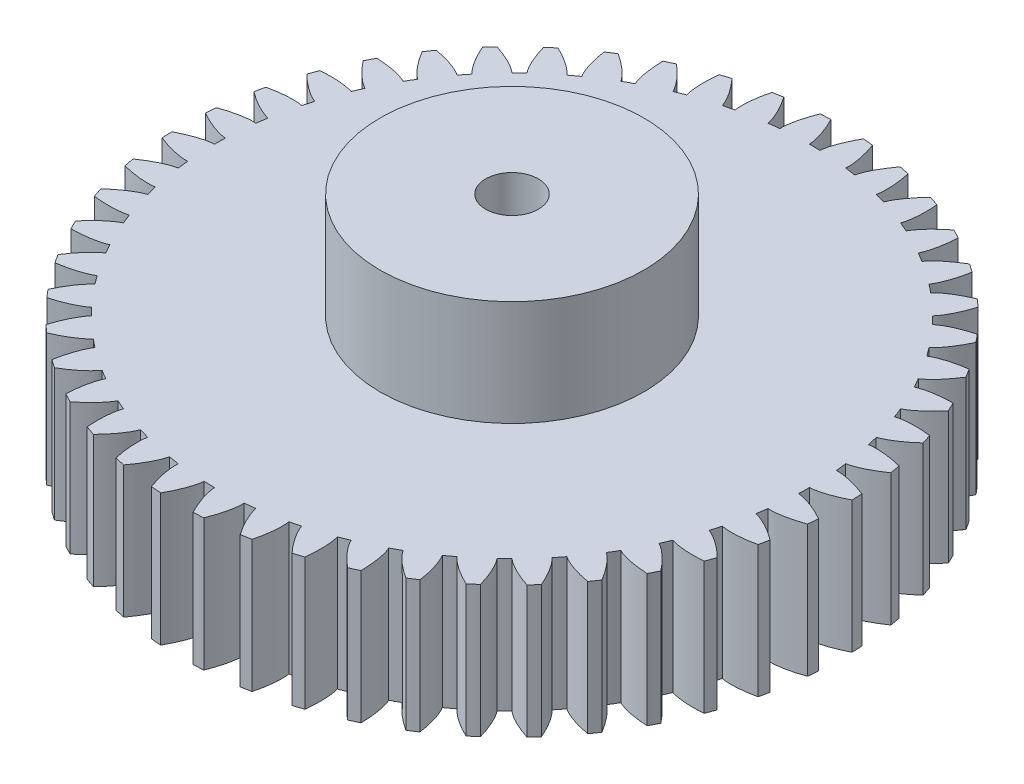
SolidWorks part; units mm, degrees
ref_plane "前视基准面" through (0, 0, 0) normal (0, 0, 1) x (1, 0, 0)
ref_plane "上视基准面" through (0, 0, 0) normal (0, 1, 0) x (1, 0, 0)
ref_plane "右视基准面" through (0, 0, 0) normal (1, 0, 0) x (0, 0, -1)
sketch "草图2" plane through (0, 0, 0) normal (0, 1, 0) x (1, 0, 0)
  line L0 (0, 0) -> (24.9716, 1.1903) construction
  circle A0 centre (0, 0) radius 22.5526
  circle A3 centre (0, 0) radius 22.75
  circle A4 centre (0, 0) radius 24
  circle A5 centre (0, 0) radius 25
  spline S0 degree 4 poles (22.5526, 0) (22.5955, 0.0016) (22.681, 0.0075) (22.8513, 0.0297) (23.0958, 0.0771) (23.3707, 0.1464) (23.7487, 0.2626) (24.2436, 0.4462) (24.853, 0.7215) (25.8766, 1.2808) (27.2095, 2.2131) (28.8963, 3.738) (30.7464, 5.9989) (32.4009, 8.7486) (33.7574, 11.9288) (34.7099, 15.2504) (35.2812, 18.6573) (35.5037, 22.2747) (35.3107, 26.7587) (34.3964, 32.0406) (32.4491, 37.9592) (29.2961, 44.1201) (25.7925, 49.0558) (22.3376, 52.9154) (19.1945, 55.868) (16.536, 58.0666) (13.7473, 60.0973) (10.8418, 61.9567) (7.0797, 64.0637) (2.3817, 66.2407) (-3.3153, 68.2632) (-8.7747, 69.5649) (-13.035, 70.2374) (-16.0345, 70.5567) (-17.5393, 70.6787) (-18.8271, 70.7566) (-19.8317, 70.8003) (-20.5292, 70.8236) (-21.1801, 70.8385) (-21.6938, 70.8472) (-22.3718, 70.8518) (-22.8561, 70.8514) (-23.6482, 70.8449) (-24.2602, 70.8313) (-25.0054, 70.8109) (-25.6707, 70.7837) (-26.3828, 70.7499) (-27.0679, 70.7093) (-27.9403, 70.6502) (-28.9771, 70.566) (-30.191, 70.4485) (-31.5713, 70.2879) (-32.6065, 70.1479) (-33.2939, 70.0459) (-33.6379, 69.9928) knots 0 0 0 0 0 0.001401 0.002802 0.005604 0.008133 0.010661 0.015718 0.022839 0.02996 0.048734 0.068727 0.096889 0.125051 0.153212 0.181374 0.209535 0.237696 0.271429 0.327752 0.384075 0.440398 0.496721 0.524883 0.553044 0.581206 0.609367 0.637529 0.66569 0.722013 0.778336 0.834659 0.84874 0.86282 0.876901 0.883942 0.890982 0.895509 0.900036 0.904564 0.909091 0.914773 0.920455 0.926136 0.931818 0.9375 0.943182 0.948864 0.954545 0.965909 0.977273 0.988636 1 1 1 1 1 construction
  spline S1 degree 4 poles (22.5526, 0) (22.5955, 0.0016) (22.681, 0.0075) (22.8513, 0.0297) (23.0958, 0.0771) (23.3707, 0.1464) (23.7487, 0.2626) (24.2436, 0.4462) (24.853, 0.7215) (25.8766, 1.2808) (27.2095, 2.2131) (28.8963, 3.738) (30.7464, 5.9989) (32.4009, 8.7486) (33.7574, 11.9288) (34.7099, 15.2504) (35.2812, 18.6573) (35.5037, 22.2747) (35.3107, 26.7587) (34.3964, 32.0406) (32.4491, 37.9592) (29.2961, 44.1201) (25.7925, 49.0558) (22.3376, 52.9154) (19.1945, 55.868) (16.536, 58.0666) (13.7473, 60.0973) (10.8418, 61.9567) (7.0797, 64.0637) (2.3817, 66.2407) (-3.3153, 68.2632) (-8.7747, 69.5649) (-13.035, 70.2374) (-16.0345, 70.5567) (-17.5393, 70.6787) (-18.8271, 70.7566) (-19.8317, 70.8003) (-20.5292, 70.8236) (-21.1801, 70.8385) (-21.6938, 70.8472) (-22.1718, 70.8504) (-22.4267, 70.8512) (-22.5526, 70.8512) knots 0 0 0 0 0 0.001401 0.002802 0.005604 0.008133 0.010661 0.015718 0.022839 0.02996 0.048734 0.068727 0.096889 0.125051 0.153212 0.181374 0.209535 0.237696 0.271429 0.327752 0.384075 0.440398 0.496721 0.524883 0.553044 0.581206 0.609367 0.637529 0.66569 0.722013 0.778336 0.834659 0.84874 0.86282 0.876901 0.883942 0.890982 0.895509 0.900036 0.904564 0.909091 0.909091 0.909091 0.909091 0.909091
  spline S2 degree 4 poles (22.4504, 2.1452) (22.4932, 2.1476) (22.5789, 2.1499) (22.7505, 2.144) (22.9984, 2.1201) (23.2787, 2.0772) (23.666, 1.9975) (24.1761, 1.8618) (24.8089, 1.6457) (25.8811, 1.1863) (27.2966, 0.385) (29.1209, -0.9725) (31.1776, -3.0471) (33.0861, -5.627) (34.739, -8.6638) (36.0032, -11.8798) (36.8959, -15.2168) (37.4614, -18.7966) (37.6958, -23.2787) (37.2881, -28.6236) (35.9126, -34.7006) (33.3599, -41.1334) (30.3416, -46.3801) (27.2695, -50.5508) (24.4215, -53.789) (21.9842, -56.2305) (19.4013, -58.5172) (16.6858, -60.6446) (13.1412, -63.0998) (8.6716, -65.7138) (3.1927, -68.269) (-2.1181, -70.0841) (-6.295, -71.1588) (-9.2506, -71.762) (-10.7369, -72.0266) (-12.0115, -72.2266) (-13.0074, -72.3657) (-13.6996, -72.4552) (-14.3461, -72.5319) (-14.8566, -72.5894) (-15.3322, -72.6381) (-15.5858, -72.6631) (-15.7112, -72.6751) knots 0 0 0 0 0 0.001401 0.002802 0.005604 0.008133 0.010661 0.015718 0.022839 0.02996 0.048734 0.068727 0.096889 0.125051 0.153212 0.181374 0.209535 0.237696 0.271429 0.327752 0.384075 0.440398 0.496721 0.524883 0.553044 0.581206 0.609367 0.637529 0.66569 0.722013 0.778336 0.834659 0.84874 0.86282 0.876901 0.883942 0.890982 0.895509 0.900036 0.904564 0.909091 0.909091 0.909091 0.909091 0.909091
  point P6 (24.8594, 2.6476)
  point P12 (23.8237, 2.9041)
  point P14 (23.9973, 0.3577)
  point P15 (24.9871, 0.8041)
  point P19 (23.9728, 1.1427)
  dimension "D1" = 45.5
  dimension "D2" = 45.1052
  dimension "D3" = 48
  dimension "D4" = 50
  dimension "D6" = 0.7854
extrude "凸台-拉伸1" add sketch "草图2" along normal blind 10 contours S2 A4 S1 A5 | S2 A3 S1 A4 | S2 A0 S1 A3 | A0 region at (0, 0, 0) region at (22.6171, 0, -1.0781) region at (23.3108, 0, -1.1112) region at (24.4138, 0, -1.1637)
pattern_circular "阵列(圆周)1" count 48 every 7.5 about axis through (0, 10, 0) along (0, -1, 0) of "凸台-拉伸1"
sketch "草图3" plane through (0, 10, 0) normal (0, 1, 0) x (1, 0, 0)
  circle A0 centre (0, 0) radius 2
  dimension "D1" = 4
extrude "切除-拉伸1" cut sketch "草图3" against normal through all contours A0 region at (0, 10, 0)
sketch "草图4" plane through (0, 10, 0) normal (0, 1, 0) x (1, 0, 0)
  circle A0 centre (0, 0) radius 10
  circle A1 centre (0, 0) radius 2
  dimension "D1" = 20
extrude "凸台-拉伸2" add sketch "草图4" along normal blind 8
equation "\"m\"= 1'齿轮模数"
equation "\"z\"= 48'齿轮齿数"
equation "\"D\"= \"m\" * \"z\"'分度圆直径"
equation "\"Db\"= \"D\" * cos ( 20 )'基圆直径"
equation "\"Df\"= ( \"z\" - 2.5 ) * \"m\"'齿根圆直径"
equation "\"Da\"= ( \"z\" + 2 ) * \"m\"'齿顶圆直径"
equation "\"D1@草图2\"= \"Df\"'齿根圆"
equation "\"D2@草图2\"= \"Db\"'基圆"
equation "\"s\"= \"m\" * pi / 2'齿厚"
equation "\"D3@草图2\"= \"D\"'分度圆"
equation "\"D4@草图2\"= \"Da\"'齿顶圆"
equation "\"D6@草图2\"= \"s\" * 0.5"
